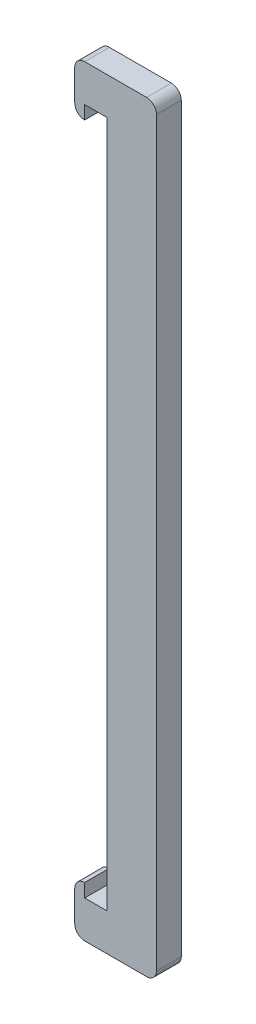
SolidWorks part; units mm, degrees
ref_plane "Front Plane" through (0, 0, 0) normal (0, 0, 1) x (1, 0, 0)
ref_plane "Top Plane" through (0, 0, 0) normal (0, 1, 0) x (1, 0, 0)
ref_plane "Right Plane" through (0, 0, 0) normal (1, 0, 0) x (0, 0, -1)
sketch "Sketch1" plane through (0, 0, 0) normal (0, 0, 1) x (1, 0, 0)
  line L0 (-8.24, 97.536) -> (-8.24, 84.582)
  line L1 (-8.24, 84.582) -> (-5.7, 84.582)
  line L2 (0, 88.011) -> (0, -88.011)
  line L3 (-5.7, 84.582) -> (-5.7, 88.011)
  line L4 (12.7, 97.536) -> (12.7, -97.536)
  line L5 (-5.7, 88.011) -> (0, 88.011)
  line L6 (12.7, -97.536) -> (-8.24, -97.536)
  line L7 (12.7, 97.536) -> (-8.24, 97.536)
  line L8 (0, 0) -> (12.7, 0) construction
  line L9 (-5.7, -88.011) -> (0, -88.011)
  line L10 (-5.7, -84.582) -> (-5.7, -88.011)
  line L11 (-8.24, -84.582) -> (-5.7, -84.582)
  line L12 (-8.24, -97.536) -> (-8.24, -84.582)
  dimension "D1" = 176.022
  dimension "D2" = 3.429
  dimension "D3" = 9.525
  dimension "D4" = 12.7
  dimension "D5" = 5.7
  dimension "D6" = 2.54
extrude "Boss-Extrude1" add sketch "Sketch1" along normal mid plane 6.35
fillet "Fillet1" radius 2.54 6 edges at (12.7, -97.536, 0) (-8.24, -97.536, 0) (-8.24, -84.582, 0) (12.7, 97.536, 0) (-8.24, 84.582, 0) (-8.24, 97.536, 0)
